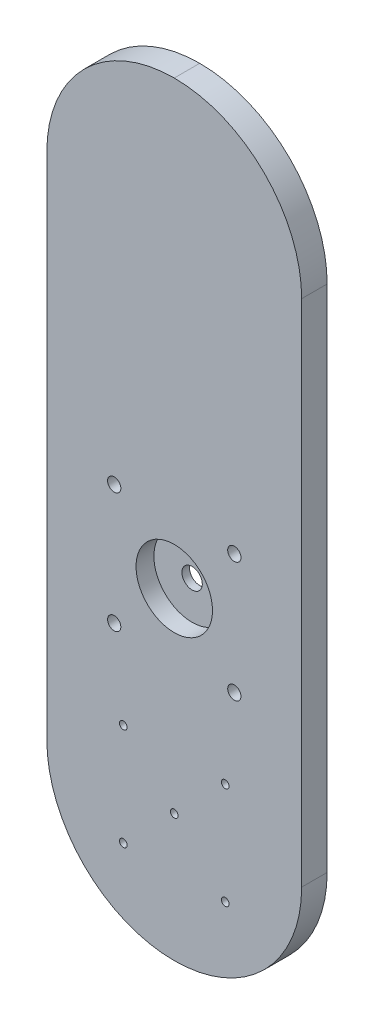
SolidWorks part; units mm, degrees
material "6061 Legierung"
ref_plane "Ebene vorne" through (0, 0, 0) normal (0, 0, 1) x (1, 0, 0)
ref_plane "Ebene oben" through (0, 0, 0) normal (0, 1, 0) x (1, 0, 0)
ref_plane "Ebene rechts" through (0, 0, 0) normal (1, 0, 0) x (0, 0, -1)
sketch "Skizze1" plane through (0, 0, 0) normal (0, 0, 1) x (1, 0, 0)
  line L0 (0, 0) -> (0, 50000) construction
  line L1 (-50, 250) -> (50, 250)
  line L2 (-50, 250) -> (-50, -50)
  line L3 (-50, -50) -> (50, -50)
  line L4 (50, 250) -> (50, -50)
  line L5 (-50, 250) -> (50, -50) construction
  line L6 (-50, -50) -> (50, 250) construction
  point P0 (0, 100)
  point P8 (0, -50)
  dimension "D1" = 100
  dimension "D2" = 300
  dimension "D3" = 50
extrude "Aufsatz-Linear austragen1" add sketch "Skizze1" along normal blind 10
fillet "Verrundung1" radius 50 4 edges at (50, -50, 5) (-50, -50, 5) (-50, 250, 5) (50, 250, 5)
sketch "RiemenSchema" plane through (0, 0, 10) normal (0, 0, 1) x (1, 0, 0)
  line L0 (-37.0077, 193.2123) -> (-15.0932, 73.7317)
  line L1 (37.0077, 193.2123) -> (15.0932, 73.7317)
  line L3 (-28.5, 48) -> (28.5, 48) construction
  line L4 (-28.5, 48) -> (-28.5, 105) construction
  line L5 (-28.5, 105) -> (28.5, 105) construction
  line L6 (28.5, 48) -> (28.5, 105) construction
  line L7 (-28.5, 48) -> (28.5, 105) construction
  line L8 (-28.5, 105) -> (28.5, 48) construction
  circle A0 centre (0, 0) radius 76.5 construction
  circle A1 centre (0, 200) radius 50 construction
  circle A2 centre (0, 200) radius 37.625
  circle A3 centre (0, 76.5) radius 15.345
  dimension "D1" = 153
  dimension "D2" = 75.25
  dimension "D3" = 30.69
  dimension "D4" = 57
  dimension "D5" = 57
hole_wizard "Ø3.0 (3) Durchmesser Bohrung1" positions "Skizze3" profile "Skizze4" hole size "Ø3.0" standard "ISO" end condition through all
sketch "Skizze3" plane through (0, 0, 10) normal (0, 0, 1) x (1, 0, 0)
  line L1 (-20, -20) -> (20, -20)
  line L2 (-20, -20) -> (-20, 20)
  line L3 (-20, 20) -> (20, 20)
  line L4 (20, -20) -> (20, 20)
  line L5 (-20, -20) -> (20, 20) construction
  line L6 (-20, 20) -> (20, -20) construction
  point P1 (0, 0)
  point P2 (20, 20)
  point P37 (-20, -20)
  point P38 (-20, 20)
  point P39 (20, -20)
  point P51 (121.9963, 109.0985)
  dimension "D1" = 40
  dimension "D2" = 40
sketch "Skizze4" plane through (0, 0, 10) normal (1, 0, 0) x (0, -1, 0)
  line L0 (0, 0) -> (0, 10)
  line L1 (0, 10) -> (1.5, 10)
  line L2 (1.5, 10) -> (1.5, 0)
  line L5 (1.5, 0) -> (0, 0)
  line L11 (0, -6.35) -> (0, 107.95) construction
  dimension "Bohrerdurchmesser" = 3
  dimension "Bohrungstiefe" = 10
hole_wizard "Ø5.2 (5.2) Durchmesser Bohrung2" positions "Skizze9" profile "Skizze8" hole size "Ø5.2" standard "ISO" end condition through all
sketch "Skizze9" plane through (0, 0, 10) normal (0, 0, 1) x (1, 0, 0)
  line L1 (-23.57, 52.93) -> (23.57, 52.93)
  line L2 (-23.57, 52.93) -> (-23.57, 100.07)
  line L3 (-23.57, 100.07) -> (23.57, 100.07)
  line L4 (23.57, 52.93) -> (23.57, 100.07)
  line L5 (-28.5, 48) -> (28.5, 105) construction
  line L6 (-28.5, 105) -> (28.5, 48) construction
  point P1 (-23.57, 52.93)
  point P2 (23.57, 100.07)
  point P295 (-23.57, 100.07)
  point P296 (23.57, 52.93)
  dimension "D1" = 47.14
sketch "Skizze8" plane through (-23.57, 52.93, 10) normal (1, 0, 0) x (0, -1, 0)
  line L0 (0, 0) -> (0, 10)
  line L1 (0, 10) -> (2.6, 10)
  line L2 (2.6, 10) -> (2.6, 0)
  line L5 (2.6, 0) -> (0, 0)
  line L11 (0, -6.35) -> (0, 107.95) construction
  dimension "Bohrerdurchmesser" = 5.2
  dimension "Bohrungstiefe" = 10
sketch "Skizze11" plane through (0, 0, 10) normal (0, 0, 1) x (1, 0, 0)
  circle A0 centre (0, 76.5) radius 15
  dimension "D1" = 30
extrude "Schnitt-Linear austragen1" cut sketch "Skizze11" against normal blind 7
hole_wizard "Ø8.0 (8) Durchmesser Bohrung1" positions "Skizze12" profile "Skizze13" hole size "Ø8.0" standard "ISO" end condition through all
sketch "Skizze12" plane through (0, 0, 10) normal (0, 0, 1) x (1, 0, 0)
  point P0 (0, 76.5)
sketch "Skizze13" plane through (0, 76.5, 10) normal (1, 0, 0) x (0, -1, 0)
  line L0 (0, 0) -> (0, 10)
  line L1 (0, 10) -> (4, 10)
  line L2 (4, 10) -> (4, 0)
  line L5 (4, 0) -> (0, 0)
  line L11 (0, -6.35) -> (0, 107.95) construction
  dimension "Bohrerdurchmesser" = 8
  dimension "Bohrungstiefe" = 10
sketch "Skizze14" plane through (0, 0, 10) normal (0, 0, 1) x (1, 0, 0)
  line L0 (-28.5, 105) -> (28.5, 48) construction
  circle A0 centre (0, 76.5) radius 19.1
  dimension "D1" = 38.2
